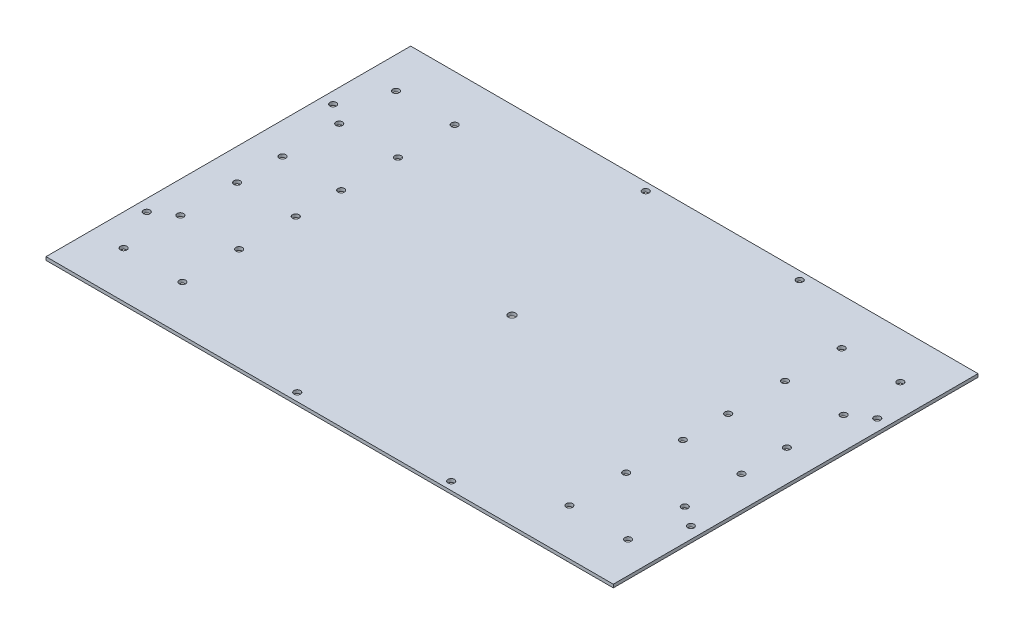
SolidWorks part; units mm, degrees
material "1345 Alloy"
ref_plane "Front Plane" through (0, 0, 0) normal (0, 0, 1) x (1, 0, 0)
ref_plane "Top Plane" through (0, 0, 0) normal (0, 1, 0) x (1, 0, 0)
ref_plane "Right Plane" through (0, 0, 0) normal (1, 0, 0) x (0, 0, -1)
other "Center of Mass"
sketch "Sketch2" plane through (0, 0, 0) normal (0, 1, 0) x (1, 0, 0)
  line L1 (-350, 225) -> (350, 225)
  line L2 (-350, 225) -> (-350, -225)
  line L3 (-350, -225) -> (350, -225)
  line L4 (350, 225) -> (350, -225)
  line L5 (-350, 225) -> (350, -225) construction
  line L6 (-350, -225) -> (350, 225) construction
  point P0 (0, 0)
  dimension "D1" = 700
  dimension "D2" = 450
extrude "Boss-Extrude1" add sketch "Sketch2" along normal mid plane 4
sketch "Sketch6" plane through (0, 2, 0) normal (0, 1, 0) x (1, 0, 0)
  circle A0 centre (-311.2031, 168) radius 4
  circle A1 centre (-238.7931, 168) radius 4
  circle A2 centre (-238.7931, 98) radius 4
  circle A3 centre (-311.2031, 98) radius 4
  circle A4 centre (-311.2031, 28) radius 4
  circle A5 centre (-238.7931, 28) radius 4
  circle A6 centre (238.7931, 168) radius 4
  circle A7 centre (311.2031, 168) radius 4
  circle A8 centre (311.2031, 98) radius 4
  circle A9 centre (238.7931, 98) radius 4
  circle A10 centre (238.7931, 28) radius 4
  circle A11 centre (311.2031, 28) radius 4
  circle A12 centre (-311.2031, -28) radius 4
  circle A13 centre (-238.7931, -28) radius 4
  circle A14 centre (-238.7931, -98) radius 4
  circle A15 centre (-311.2031, -98) radius 4
  circle A16 centre (-311.2031, -168) radius 4
  circle A17 centre (-238.7931, -168) radius 4
  circle A18 centre (238.7931, -28) radius 4
  circle A19 centre (311.2031, -28) radius 4
  circle A20 centre (311.2031, -98) radius 4
  circle A21 centre (238.7931, -98) radius 4
  circle A22 centre (238.7931, -168) radius 4
  circle A23 centre (311.2031, -168) radius 4
  dimension "D1" = 8
  dimension "D2" = 8
  dimension "D3" = 8
  dimension "D4" = 8
  dimension "D5" = 8
  dimension "D6" = 8
  dimension "D7" = 8
  dimension "D8" = 8
  dimension "D9" = 8
  dimension "D10" = 8
  dimension "D11" = 8
  dimension "D12" = 8
  dimension "D13" = 8
  dimension "D14" = 8
  dimension "D15" = 8
  dimension "D16" = 8
  dimension "D17" = 8
  dimension "D18" = 8
  dimension "D19" = 8
  dimension "D20" = 8
  dimension "D21" = 8
  dimension "D22" = 8
  dimension "D23" = 8
  dimension "D24" = 8
extrude "Cut-Extrude2" cut sketch "Sketch6" against normal through all
sketch "Sketch8" plane through (0, 2, 0) normal (0, 1, 0) x (1, 0, 0)
  line L0 (-350, 225) -> (350, -225) construction
  line L1 (350, 225) -> (-350, -225) construction
  circle A0 centre (0, 0) radius 4.5
  dimension "D1" = 9
extrude "Cut-Extrude4" cut sketch "Sketch8" against normal up to next
sketch "Sketch9" plane through (0, 2, 0) normal (0, 1, 0) x (1, 0, 0)
  line L0 (-50, -215) -> (140, -215) construction
  line L1 (-50, 215) -> (-50, -215) construction
  line L2 (140, -215) -> (140, 215) construction
  line L5 (-350, 215) -> (-50, 215) construction
  line L6 (-350, 225) -> (-350, -225) construction
  circle A0 centre (-50, -215) radius 4
  circle A1 centre (140, -215) radius 4
  circle A2 centre (-50, 215) radius 4
  circle A3 centre (140, 215) radius 4
  dimension "D1" = 8
  dimension "D2" = 8
  dimension "D3" = 8
  dimension "D4" = 8
  dimension "D5" = 300
  dimension "D6" = 190
extrude "Cut-Extrude5" cut sketch "Sketch9" against normal through all
sketch "Sketch10" plane through (0, 2, 0) normal (0, 1, 0) x (1, 0, 0)
  line L0 (-350, 225) -> (-335.68, 225) construction
  line L1 (350, 225) -> (-350, 225) construction
  line L2 (-335.68, 225) -> (-335.68, 115) construction
  line L3 (-350, -225) -> (-335.68, -225) construction
  line L4 (-350, -225) -> (350, -225) construction
  line L5 (-335.68, -225) -> (-335.68, -115) construction
  line L6 (350, 225) -> (335.68, 225) construction
  line L7 (335.68, 225) -> (335.68, 115) construction
  line L8 (350, -225) -> (335.68, -225) construction
  line L9 (335.68, -225) -> (335.68, -115) construction
  circle A0 centre (-335.68, 115) radius 4
  circle A1 centre (-335.68, -115) radius 4
  circle A2 centre (335.68, 115) radius 4
  circle A3 centre (335.68, -115) radius 4
  dimension "D5" = 8
  dimension "D6" = 8
  dimension "D1" = 14.32
  dimension "D2" = 14.32
  dimension "D3" = 110
  dimension "D4" = 110
  dimension "D7" = 14.32
  dimension "D8" = 110
  dimension "D9" = 14.32
  dimension "D10" = 110
extrude "Cut-Extrude6" cut sketch "Sketch10" against normal through all both
sketch "Sketch11" plane through (0, 2, 0) normal (0, 1, 0) x (1, 0, 0)
  line L0 (-350, -182.66) -> (-230, -182.66)
  line L1 (-350, 225) -> (-230, 225)
  line L2 (-350, 225) -> (-350, 182.66)
  line L3 (-350, 182.66) -> (-230, 182.66)
  line L4 (-230, 225) -> (-230, 182.66)
  line L5 (-350, -182.66) -> (-350, -225)
  line L6 (-350, -225) -> (-230, -225)
  line L7 (-230, -182.66) -> (-230, -225)
  line L8 (230, -182.66) -> (350, -182.66)
  line L9 (230, -182.66) -> (230, -225)
  line L10 (230, -225) -> (350, -225)
  line L11 (350, -182.66) -> (350, -225)
  line L12 (230, 225) -> (350, 225)
  line L13 (230, 225) -> (230, 182.66)
  line L14 (230, 182.66) -> (350, 182.66)
  line L15 (350, 225) -> (350, 182.66)
  dimension "D1" = 42.34
  dimension "D2" = 120
  dimension "D3" = 120
  dimension "D4" = 120
  dimension "D5" = 42.34
  dimension "D6" = 120
  dimension "D7" = 42.34
  dimension "D8" = 42.34
extrude "Cut-Extrude7" [suppressed] cut sketch "Sketch11" against normal blind 10
